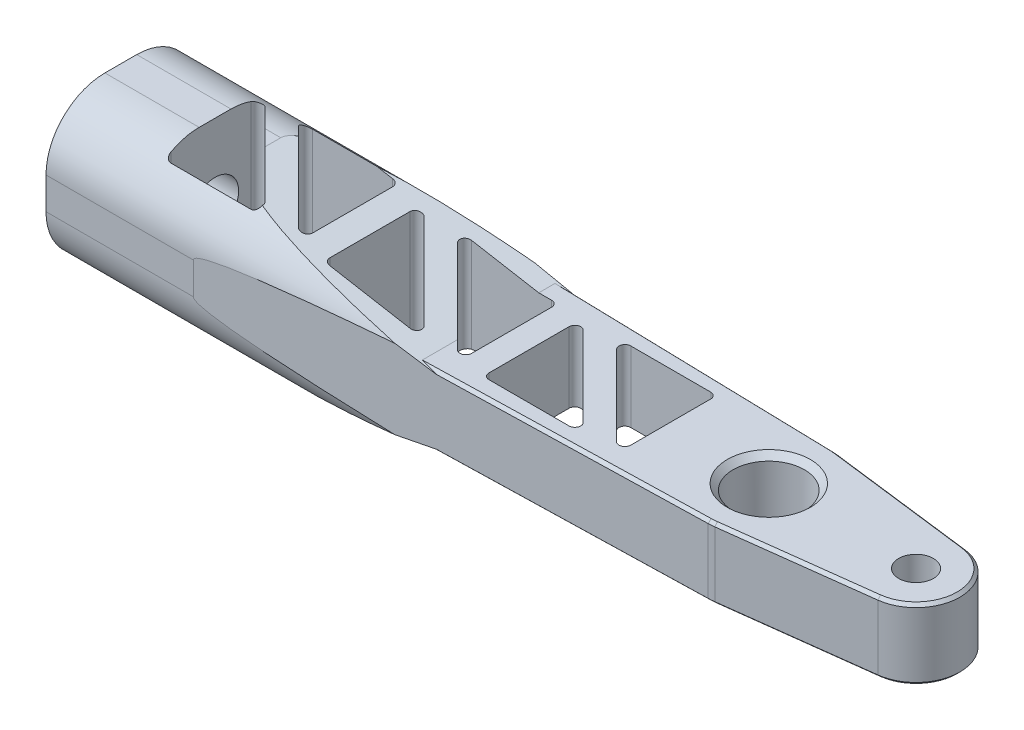
SolidWorks part; units mm, degrees
ref_plane "Front Plane" through (0, 0, 0) normal (0, 0, 1) x (1, 0, 0)
ref_plane "Top Plane" through (0, 0, 0) normal (0, 1, 0) x (1, 0, 0)
ref_plane "Right Plane" through (0, 0, 0) normal (1, 0, 0) x (0, 0, -1)
sketch "Sketch1" plane through (0, 0, 0) normal (0, 1, 0) x (1, 0, 0)
  line L1 (-67.5, -12.7) -> (67.5, -12.7)
  line L2 (-67.5, -12.7) -> (-67.5, 12.7)
  line L3 (-67.5, 12.7) -> (67.5, 12.7)
  line L5 (-67.5, -12.7) -> (67.5, 12.7) construction
  line L6 (-67.5, 12.7) -> (67.5, -12.7) construction
  arc A0 (67.5, -12.7) -> (67.5, 12.7) centre (67.5, 0) ccw
  circle A1 centre (67.5, 0) radius 2.95
  circle A2 centre (42.5, 0) radius 6.05
  point P0 (0, 0)
  dimension "D4" = 12.1
  dimension "D5" = 5.9
  dimension "D1" = 25.4
  dimension "D2" = 110
  dimension "D3" = 25
extrude "Boss-Extrude1" add sketch "Sketch1" along normal blind 12.7 and the other way blind 12.7 contours A2 | A1 | L3 A0 L1 L2 region at (67.5, 0, 0) region at (42.5, 0, 0)
sketch "Sketch6" plane through (0, 12.7, 0) normal (0, 1, 0) x (1, 0, 0)
  line L1 (-67.5, -12.7) -> (67.5, -12.7) construction
  line L4 (43.8082, -10.4686) -> (68.4238, -7.3925)
  line L6 (-67.5, 12.7) -> (67.5, 12.7) construction
  line L7 (-67.5, -12.7) -> (67.5, -12.7)
  line L8 (43.8082, 10.4686) -> (68.4238, 7.3925)
  line L9 (-67.5, 12.7) -> (67.5, 12.7)
  line L10 (42.7664, 10.5466) -> (-42.5, 12.7)
  line L11 (42.7664, -10.5466) -> (-42.5, -12.7)
  line L12 (-67.5, -12.7) -> (-67.5, 12.7) construction
  arc A4 (67.5, -12.7) -> (67.5, 12.7) centre (67.5, 0) ccw construction
  arc A5 (67.5, -12.7) -> (67.5, 12.7) centre (67.5, 0) ccw
  circle A10 centre (42.5, 0) radius 10.55
  circle A11 centre (42.5, 0) radius 10.55
  circle A13 centre (67.5, 0) radius 7.45
  circle A14 centre (67.5, 0) radius 7.45
  arc M8 (67.5, -12.7) -> (67.5, 12.7) centre (67.5, 0) ccw
  line M9 (67.5, 12.7) -> (-67.5, 12.7)
  dimension "D3" = 25
  dimension "D1" = 4.5
  dimension "D2" = 4.5
extrude "Cut-Extrude4" cut sketch "Sketch6" against normal through all contours A14 L4 A11 L11 L7 L10 L8 M8 M9 region at (56.2714, 12.7, 10.1739)
sketch "Sketch2" plane through (0, 0, -12.7) normal (0, 0, -1) x (-1, 0, 0)
  line L0 (67.5, -12.7) -> (42.5, -12.7) construction
  line L1 (-74.95, 12.7) -> (43.0476, 12.7)
  line L2 (-74.95, 12.7) -> (-74.95, 6)
  line L3 (-74.95, 6) -> (5.05, 6)
  line L5 (-74.95, -12.7) -> (43.0476, -12.7)
  line L6 (-74.95, -12.7) -> (-74.95, -6)
  line L7 (-74.95, -6) -> (5.05, -6)
  line L9 (67.5, 12.7) -> (42.5, 12.7) construction
  line L10 (5.05, 6) -> (43.0476, 12.7)
  line L11 (5.05, -6) -> (43.0476, -12.7)
  line L13 (-74.95, 12.7) -> (-74.95, -12.7) construction
  dimension "D1" = 12
  dimension "D2" = 10
  dimension "D3" = 10
  dimension "D4" = 80
extrude "Cut-Extrude1" cut sketch "Sketch2" against normal through all
fillet "Fillet8" radius 10 4 edges at (-55.2738, -12.7, 12.7) (-55.2738, 12.7, 12.7) (-55.2738, -12.7, -12.7) (-55.2738, 12.7, -12.7)
sketch "Sketch7" plane through (0, 12.7, 0) normal (0, 1, 0) x (1, 0, 0)
  line L0 (-51.5, 8.5) -> (-51.5, -8.5)
  line L1 (-51.5, -8.5) -> (-34.5, -8.5)
  line L2 (-34.5, -8.5) -> (-51.5, 8.5)
  line L3 (-45.8431, 8.5) -> (-28.8431, -8.5)
  line L4 (-28.8431, -8.5) -> (-28.8431, 8.5)
  line L5 (-28.8431, 8.5) -> (-45.8431, 8.5)
  line L6 (-67.5, -2.7) -> (-67.5, 2.7) construction
  point P5 (-51.5, 0)
  point P10 (-28.8431, 0)
  dimension "D1" = 17
  dimension "D2" = 16
  dimension "D3" = 4
extrude "Cut-Extrude5" cut sketch "Sketch7" against normal through all
ref_axis "Axis2" through (82.0725, 0, 0) along (-1, 0, 0)
fillet "Fillet9" radius 1 6 edges at (-28.8431, 0, -8.5) (-45.8431, 0, -8.5) (-28.8431, 0, 8.5) (-34.5, 0, 8.5) (-51.5, 0, -8.5) (-51.5, 0, 8.5)
pattern_linear "LPattern1" count 3 spacing 27 along (1, 0, 0) of "Cut-Extrude5", "Fillet9"
chamfer "Chamfer2" distance 0.5 angle 45 14 edges at (18.8582, -6, 11.1504) (43.2882, -6, 10.5205) (56.116, -6, 8.9305) (18.8582, -6, -11.1504) (74.95, -6, 0) (43.2882, -6, -10.5205) (56.116, -6, -8.9305) (18.8582, 6, 11.1504) (43.2882, 6, 10.5205) (56.116, 6, 8.9305) (74.95, 6, 0) (56.116, 6, -8.9305) (43.2882, 6, -10.5205) (18.8582, 6, -11.1504)
sketch "Sketch8" plane through (-67.5, 0, 0) normal (-1, 0, 0) x (0, 0, 1)
  circle A0 centre (0, 0) radius 4
  dimension "D1" = 8
extrude "Cut-Extrude6" cut sketch "Sketch8" against normal blind 18
chamfer "Chamfer3" distance 1 angle 45 1 edges at (42.5, 6, -6.05)
ref_plane "Plane1" through (0, -12.7, 0) normal (0, -1, 0) x (-1, 0, 0)
mirror "Mirror1" [suppressed] about plane through (0, -12.7, 0) normal (0, -1, 0) of bodies 110
delete or keep bodies "Body-Delete/Keep 1" [suppressed] type delete bodies bodies 110
ref_point "Point1"
equation "\"D1@Fillet7\"=40mm"
